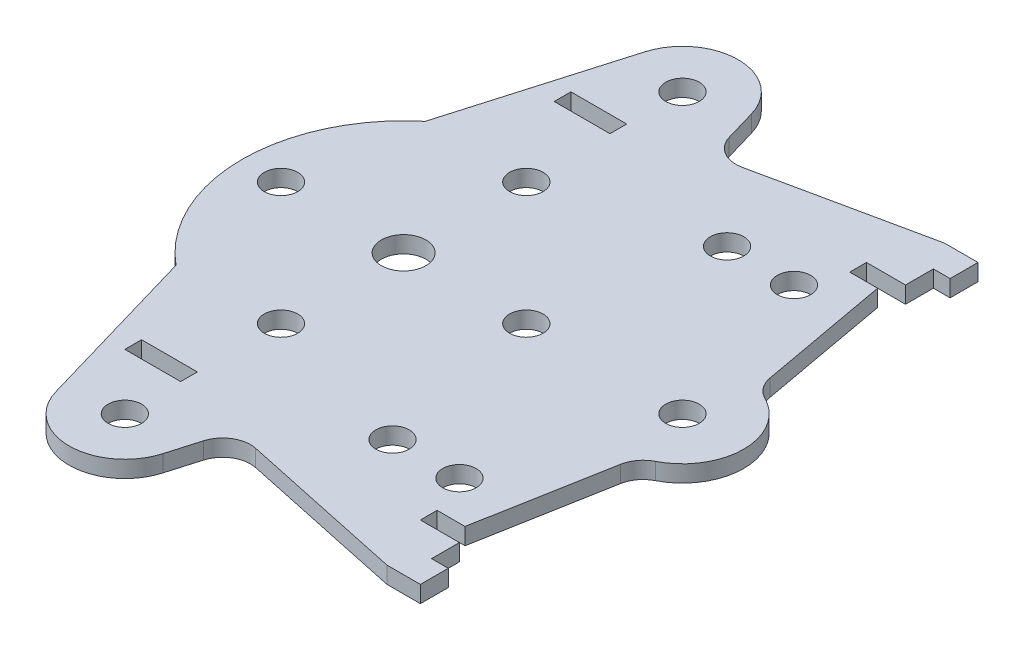
SolidWorks part; units mm, degrees
material "201 Stal nierdzewna odprężona (SS)"
ref_plane "Płaszczyzna przednia" through (0, 0, 0) normal (0, 0, 1) x (1, 0, 0)
ref_plane "Płaszczyzna górna" through (0, 0, 0) normal (0, 1, 0) x (1, 0, 0)
ref_plane "Płaszczyzna prawa" through (0, 0, 0) normal (1, 0, 0) x (0, 0, -1)
sketch "Szkic1" plane through (0, 0, 0) normal (0, 1, 0) x (1, 0, 0)
  line L0 (11.2544, 47.1278) -> (9.6, 52.8)
  line L1 (47, 50) -> (17.0949, 43.6372)
  line L2 (53, 50) -> (47, 50)
  line L3 (50, 45) -> (50, 40)
  line L4 (50, 45) -> (53, 45)
  line L5 (53, 50) -> (53, 45)
  line L6 (43, 40) -> (50, 40)
  line L7 (43, 40) -> (43, 37)
  line L8 (43, 37) -> (48, 37)
  line L9 (48, 37) -> (52.3001, 13.3831)
  line L10 (48, -37) -> (52.3001, -13.3831)
  line L11 (-18.4819, 22.3477) -> (-9.6, 52.8)
  line L12 (53, -50) -> (53, -45)
  line L13 (47, -50) -> (17.0949, -43.6372)
  line L14 (43, -37) -> (48, -37)
  line L15 (11.2544, -47.1278) -> (9.6, -52.8)
  line L16 (50, -45) -> (50, -40)
  line L17 (50, -45) -> (53, -45)
  line L18 (53, -50) -> (47, -50)
  line L19 (43, -40) -> (50, -40)
  line L20 (-18.4819, -22.3477) -> (-9.6, -52.8)
  line L21 (43, -40) -> (43, -37)
  line L22 (-10, 37) -> (0, 37)
  line L23 (-10, -37) -> (0, -37)
  line L24 (-10, -40) -> (0, -40)
  line L25 (-10, -40) -> (-10, -37)
  line L26 (-10, 40) -> (-10, 37)
  line L27 (0, 40) -> (0, 37)
  line L28 (0, -40) -> (0, -37)
  line L29 (-10, 40) -> (0, 40)
  circle A0 centre (0, 50) radius 3
  arc A1 (11.2544, 47.1278) -> (17.0949, 43.6372) centre (16.0544, 48.5278) ccw
  arc A2 (9.6, 52.8) -> (-9.6, 52.8) centre (0, 50) ccw
  arc A3 (52.3001, 13.3831) -> (54.9632, 9.8166) centre (57.2193, 14.2787) ccw
  arc A4 (54.9632, -9.8166) -> (54.9632, 9.8166) centre (50, 0) ccw
  arc A5 (54.9632, -9.8166) -> (52.3001, -13.3831) centre (57.2193, -14.2787) ccw
  arc A6 (-18.4819, 22.3477) -> (-18.4819, -22.3477) centre (0, 0) ccw
  arc A7 (-9.6, -52.8) -> (9.6, -52.8) centre (0, -50) ccw
  circle A8 centre (0, -50) radius 3
  arc A9 (17.0949, -43.6372) -> (11.2544, -47.1278) centre (16.0544, -48.5278) ccw
  circle A10 centre (0, 22) radius 3
  circle A11 centre (0, -22) radius 3
  circle A12 centre (-22, 0) radius 3
  circle A13 centre (50, 0) radius 3
  circle A14 centre (22, 0) radius 3
  circle A15 centre (0, 0) radius 4
  circle A16 centre (40, -30) radius 3
  circle A17 centre (40, 30) radius 3
  circle A18 centre (28, -30) radius 3
  circle A19 centre (28, 30) radius 3
extrude "Dodanie-wyciągnięcie1" add sketch "Szkic1" along normal blind 3
